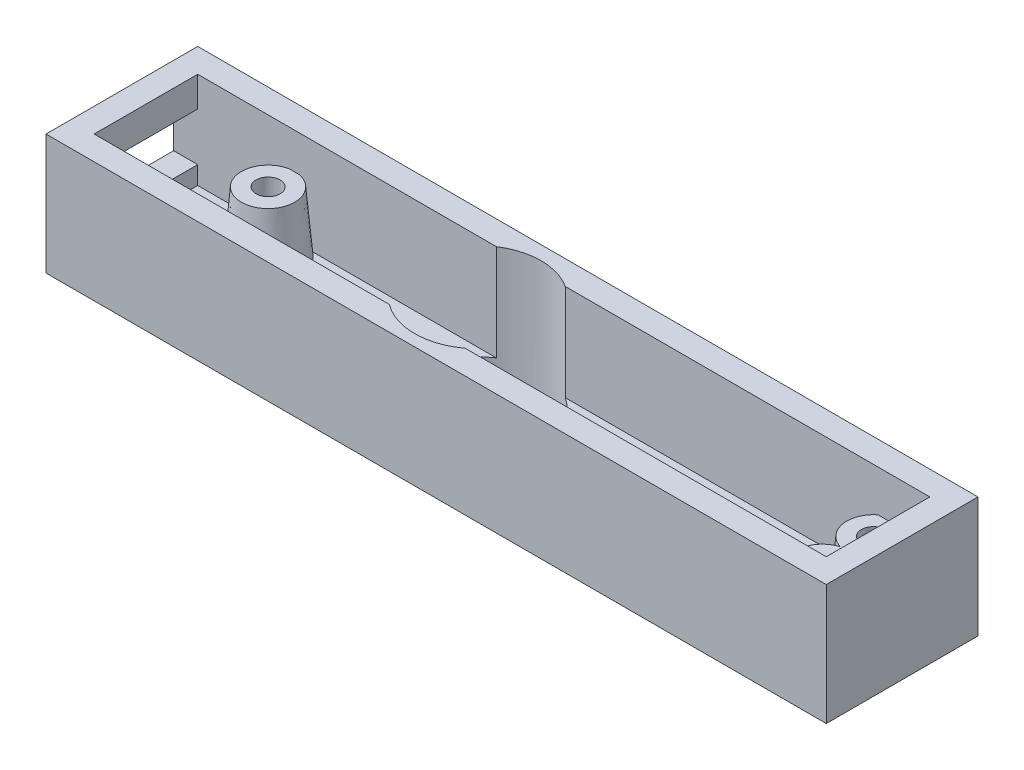
SolidWorks part; units mm, degrees
ref_plane "Front Plane" through (0, 0, 0) normal (0, 0, 1) x (1, 0, 0)
ref_plane "Top Plane" through (0, 0, 0) normal (0, 1, 0) x (1, 0, 0)
ref_plane "Right Plane" through (0, 0, 0) normal (1, 0, 0) x (0, 0, -1)
sketch "Sketch1" plane through (0, 0, 0) normal (0, 1, 0) x (1, 0, 0)
  line L1 (0, 0) -> (64.8, 0)
  line L2 (0, 0) -> (0, -12.6)
  line L3 (0, -12.6) -> (64.8, -12.6)
  line L4 (64.8, 0) -> (64.8, -12.6)
  dimension "D1" = 64.8
  dimension "D2" = 12.6
extrude "Boss-Extrude1" add sketch "Sketch1" along normal blind 2
sketch "Sketch2" plane through (0, 2, 0) normal (0, 1, 0) x (1, 0, 0)
  line L0 (2, -10.6) -> (2, -2)
  line L1 (0, -12.6) -> (64.8, -12.6)
  line L2 (0, -12.6) -> (0, 0)
  line L3 (0, 0) -> (64.8, 0)
  line L4 (64.8, -12.6) -> (64.8, 0)
  line L5 (2, -2) -> (62.8, -2)
  line L6 (62.8, -10.6) -> (62.8, -2)
  line L7 (2, -10.6) -> (62.8, -10.6)
  dimension "D1" = 2
extrude "Boss-Extrude2" add sketch "Sketch2" along normal blind 8
sketch "Sketch3" plane through (0, 0, 0) normal (0, -1, 0) x (-1, 0, 0)
  line L0 (-2.2, -2.2) -> (-2.2, -10.4)
  line L1 (0, 0) -> (-64.8, 0)
  line L2 (0, 0) -> (0, -12.6)
  line L3 (0, -12.6) -> (-64.8, -12.6)
  line L4 (-64.8, 0) -> (-64.8, -12.6)
  line L5 (-2.2, -10.4) -> (-62.6, -10.4)
  line L6 (-62.6, -2.2) -> (-62.6, -10.4)
  line L7 (-2.2, -2.2) -> (-62.6, -2.2)
  circle A0 centre (-29.66, -6.4) radius 5.25
  dimension "D4" = 10.5
  dimension "D2" = 27.46
  dimension "D3" = 4
  dimension "D1" = 2.2
extrude "Cut-Extrude1" cut sketch "Sketch3" against normal through all contours L7 A0 L5 | L5 A0 | L7 A0 region at (29.66, 0, 6.3295) region at (29.66, 0, 1.7762) region at (29.66, 0, 10.9055)
sketch "Sketch4" plane through (0, 2, 0) normal (0, 1, 0) x (1, 0, 0)
  circle A0 centre (60.3, -4.18) radius 2.65
  circle A1 centre (60.3, -8.42) radius 2.65
  circle A2 centre (10.02, -4.18) radius 2.65
  line M2 (32.81, -10.6) -> (62.8, -10.6)
  line M3 (62.8, -10.6) -> (62.8, -2)
  line M4 (62.8, -2) -> (32.524, -2)
  dimension "D1" = 5.3
  dimension "D2" = 5.3
  dimension "D3" = 5.3
extrude "Boss-Extrude3" add sketch "Sketch4" along normal blind 5 draft 5 contours A1 A0 M2 M3 | A1 A0 M3 M4 | A0 A1 | A2 region at (60.2757, 2, 4.0411) region at (60.2757, 2, 8.5589) region at (60.3, 2, 6.3) region at (10.02, 2, 4.18)
sketch "Sketch5" plane through (0, 7, 0) normal (0, 1, 0) x (1, 0, 0)
  circle A0 centre (60.3, -8.42) radius 1
  circle A1 centre (10.02, -4.18) radius 1
  circle A2 centre (60.3, -4.18) radius 1
  dimension "D1" = 2
  dimension "D2" = 2
  dimension "D3" = 2
extrude "Cut-Extrude2" cut sketch "Sketch5" against normal blind 4
sketch "Sketch6" plane through (0, 0, 0) normal (-1, 0, 0) x (0, 0, 1)
  line L0 (6.3926, 7) -> (2, 7) construction
  line L1 (2, 7.5) -> (10.6, 7.5)
  line L2 (2, 7.5) -> (2, 3.5)
  line L3 (2, 3.5) -> (10.6, 3.5)
  line L4 (10.6, 7.5) -> (10.6, 3.5)
  line L5 (0, 10) -> (0, 0) construction
  line L6 (12.6, 10) -> (12.6, 0) construction
  dimension "D1" = 0.5
  dimension "D2" = 4
  dimension "D3" = 2
  dimension "D4" = 2
extrude "Cut-Extrude3" cut sketch "Sketch6" against normal blind 3
equation "\"D1@Sketch1\"=60+4+0.8"
equation "\"D2@Sketch1\"=8+4+0.6"
equation "\"D2@Sketch3\"=23.5+7.92/2"
equation "\"D1@Sketch4\"=2.65*2"
equation "\"D2@Sketch4\"=\"D1@Sketch4\""
equation "\"D3@Sketch4\"=\"D1@Sketch4\""
